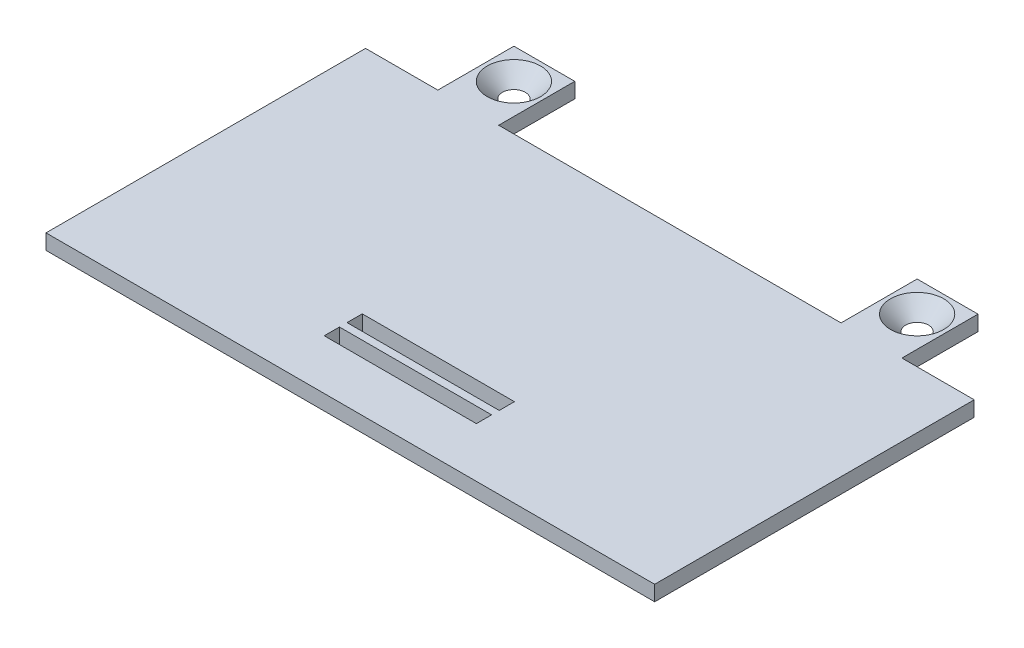
SolidWorks part; units mm, degrees
ref_plane "Front" through (0, 0, 0) normal (0, 0, 1) x (1, 0, 0)
ref_plane "Top" through (0, 0, 0) normal (0, 1, 0) x (1, 0, 0)
ref_plane "Right" through (0, 0, 0) normal (1, 0, 0) x (0, 0, -1)
sketch "Эскиз1" plane through (0, 0, 0) normal (0, 1, 0) x (1, 0, 0)
  line L1 (-158.1764, 86.5492) -> (-80.9764, 86.5492)
  line L2 (-158.1764, 86.5492) -> (-158.1764, 8.5492)
  line L3 (-158.1764, 8.5492) -> (-80.9764, 8.5492)
  line L4 (-80.9764, 86.5492) -> (-80.9764, 8.5492)
  dimension "D1" = 77.2
  dimension "D2" = 78
sketch "Эскиз4" plane through (0, 0, 0) normal (0, 1, 0) x (1, 0, 0)
  line L1 (-36.8822, 61.3775) -> (43.1178, 61.3775)
  line L2 (-36.8822, 61.3775) -> (-36.8822, 9.3775)
  line L3 (-36.8822, 9.3775) -> (43.1178, 9.3775)
  line L4 (43.1178, 61.3775) -> (43.1178, 9.3775)
  dimension "D1" = 80
  dimension "D2" = 52
extrude "Бобышка-Вытянуть2" add sketch "Эскиз4" against normal blind 2 separate body
sketch "Эскиз5" plane through (0, 0, 0) normal (0, 1, 0) x (1, 0, 0)
  line L1 (-36.8822, 61.3775) -> (-27.3822, 61.3775)
  line L2 (-36.8822, 61.3775) -> (-36.8822, 51.3775)
  line L3 (-36.8822, 51.3775) -> (-27.3822, 51.3775)
  line L4 (-27.3822, 61.3775) -> (-27.3822, 51.3775)
  point P5 (-27.3822, 56.3775)
  dimension "D1" = 9.5
  dimension "D2" = 10
extrude "Вырез-Вытянуть4" cut sketch "Эскиз5" along normal blind 35 and the other way blind 32
sketch "Эскиз6" plane through (0, 0, 0) normal (0, 1, 0) x (1, 0, 0)
  line L0 (43.1178, 61.3775) -> (-27.3822, 61.3775) construction
  line L1 (-19.3822, 61.3775) -> (25.6178, 61.3775)
  line L2 (-19.3822, 61.3775) -> (-19.3822, 51.3775)
  line L3 (-19.3822, 51.3775) -> (25.6178, 51.3775)
  line L4 (25.6178, 61.3775) -> (25.6178, 51.3775)
  line L5 (-27.3822, 51.3775) -> (-27.3822, 61.3775) construction
  dimension "D1" = 8
  dimension "D2" = 10
  dimension "D3" = 45
extrude "Вырез-Вытянуть5" cut sketch "Эскиз6" against normal blind 45 and the other way blind 54
sketch "Эскиз7" plane through (0, 0, 0) normal (0, 1, 0) x (1, 0, 0)
  line L1 (43.1178, 61.3775) -> (33.6178, 61.3775)
  line L2 (43.1178, 61.3775) -> (43.1178, 51.3775)
  line L3 (43.1178, 51.3775) -> (33.6178, 51.3775)
  line L4 (33.6178, 61.3775) -> (33.6178, 51.3775)
  dimension "D1" = 10
  dimension "D2" = 9.5
extrude "Вырез-Вытянуть6" cut sketch "Эскиз7" against normal blind 67 and the other way blind 64
sketch "Эскиз8" plane through (0, 0, 0) normal (0, 1, 0) x (1, 0, 0)
  line L0 (-19.3822, 61.3775) -> (-27.3822, 61.3775) construction
  line L1 (-19.3822, 51.3775) -> (-19.3822, 61.3775) construction
  circle A0 centre (-23.3822, 57.3775) radius 1.5
  dimension "D1" = 4
  dimension "D2" = 4
extrude "Вырез-Вытянуть7" cut sketch "Эскиз8" against normal blind 30 and the other way blind 30
chamfer "Фаска1" distance 2 angle 45 1 edges at (-23.3822, 0, -55.8775)
sketch "Эскиз9" plane through (0, 0, 0) normal (0, 1, 0) x (1, 0, 0)
  line L0 (33.6178, 61.3775) -> (25.6178, 61.3775) construction
  line L1 (25.6178, 61.3775) -> (25.6178, 51.3775) construction
  circle A0 centre (29.6178, 57.3775) radius 1.5
  dimension "D1" = 4
  dimension "D2" = 4
extrude "Вырез-Вытянуть8" cut sketch "Эскиз9" against normal blind 33 and the other way blind 20
chamfer "Фаска2" distance 2 angle 45 1 edges at (29.6178, 0, -55.8775)
sketch "Эскиз10" plane through (0, 0, 0) normal (0, 1, 0) x (1, 0, 0)
  line L0 (-36.8822, 51.3775) -> (-36.8822, 9.3775) construction
  line L1 (-6.8822, 17.9462) -> (13.1178, 17.9462)
  line L2 (-6.8822, 17.9462) -> (-6.8822, 15.9462)
  line L3 (-6.8822, 15.9462) -> (13.1178, 15.9462)
  line L4 (13.1178, 17.9462) -> (13.1178, 15.9462)
  line L5 (-6.8822, 20.9462) -> (13.1178, 20.9462)
  line L6 (-6.8822, 20.9462) -> (-6.8822, 18.9462)
  line L7 (-6.8822, 18.9462) -> (13.1178, 18.9462)
  line L8 (13.1178, 20.9462) -> (13.1178, 18.9462)
  point P4 (13.1178, 16.9462)
  dimension "D1" = 20
  dimension "D2" = 2
  dimension "D3" = 30
  dimension "D4" = 30
  dimension "D5" = 1
  dimension "D6" = 2
extrude "Вырез-Вытянуть9" cut sketch "Эскиз10" against normal blind 2
